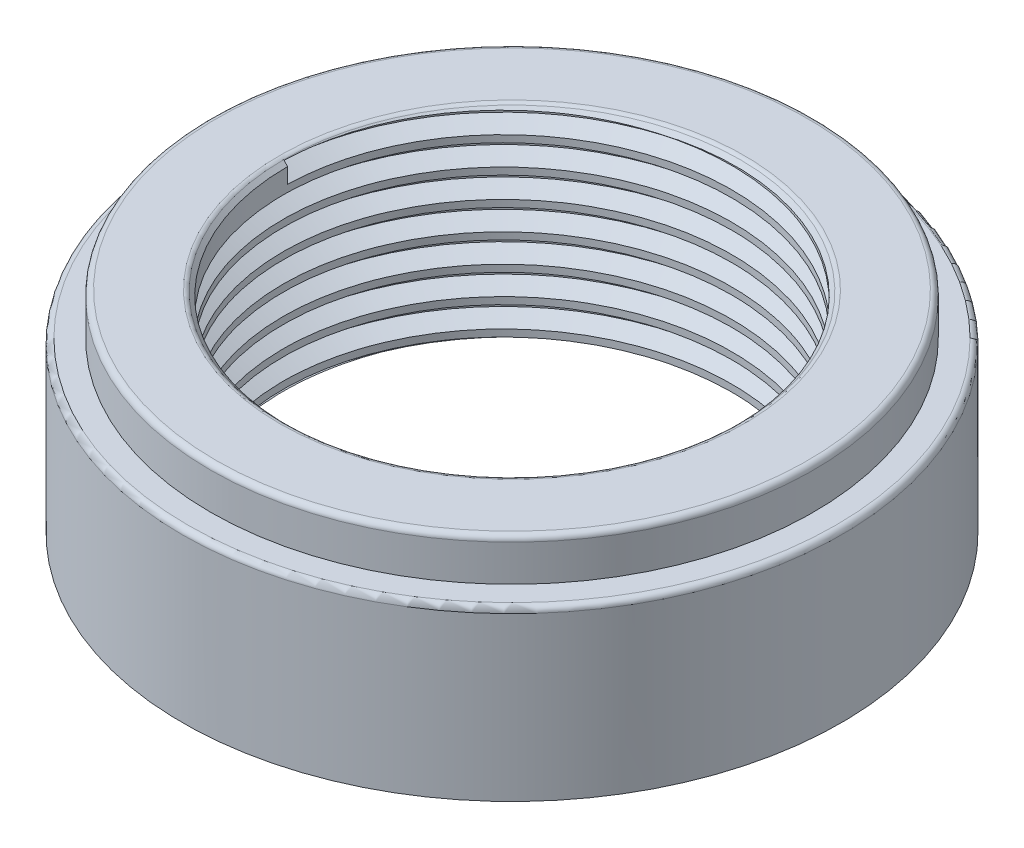
SolidWorks part; units mm, degrees
ref_plane "Front Plane" through (0, 0, 0) normal (0, 0, 1) x (1, 0, 0)
ref_plane "Top Plane" through (0, 0, 0) normal (0, 1, 0) x (1, 0, 0)
ref_plane "Right Plane" through (0, 0, 0) normal (1, 0, 0) x (0, 0, -1)
sketch "Sketch1" plane through (0, 0, 0) normal (0, 1, 0) x (1, 0, 0)
  circle A0 centre (0, 0) radius 29.845
  dimension "D1" = 59.69
extrude "Boss-Extrude1" add sketch "Sketch1" along normal blind 19.05
sketch "Sketch16" plane through (0, 19.05, 0) normal (0, 1, 0) x (1, 0, 0)
  circle A0 centre (0, 0) radius 27.305
  circle A1 centre (0, 0) radius 29.845 construction
  circle A2 centre (0, 0) radius 29.845
  dimension "D1" = 2.54
extrude "Cut-Extrude2" cut sketch "Sketch16" against normal blind 3.81
sketch "Sketch18" plane through (0, 19.05, 0) normal (0, 1, 0) x (1, 0, 0)
  circle A0 centre (0, 0) radius 20.32
  dimension "D1" = 40.64
extrude "Cut-Extrude3" cut sketch "Sketch18" against normal through all
thread "Thread2" pitch 2.54 method cut profile "Thread Profile2" start angle 0, offset 0, length 0, pitch 2.54, diameter 40.64
ref_plane "Plane2" through (-20.32, 19.05, 0) normal (0, 0, 1) x (-1, 0, 0)
sketch "Thread Profile2" plane through (-20.32, 19.05, 0) normal (0, 0, 1) x (-1, 0, 0)
  line L0 (0, 0) -> (0, 2.54) construction
  line L1 (0, 0) -> (1.3748, 0.7937)
  line L2 (1.3748, 0.7937) -> (1.3748, 1.1112)
  line L3 (1.3748, 1.1112) -> (0, 1.905)
  line L4 (1.3748, 0.9525) -> (0, 0.9525) construction
  line L11 (0, 0) -> (0, 1.905)
  point P2 (0, 0)
  dimension "Pitch" = 2.54
  dimension "Profile_Angle" = 60
  dimension "Profile_Land" = 0.3175
  dimension "Profile_Height" = 1.3748
chamfer "Chamfer4" distance 0.508 angle 45 1 edges at (-20.32, 19.05, 0)
fillet "Fillet3" radius 0.508 3 edges at (0, 15.24, 29.845) (0, 19.05, 27.305) (0, 19.05, 20.828)
